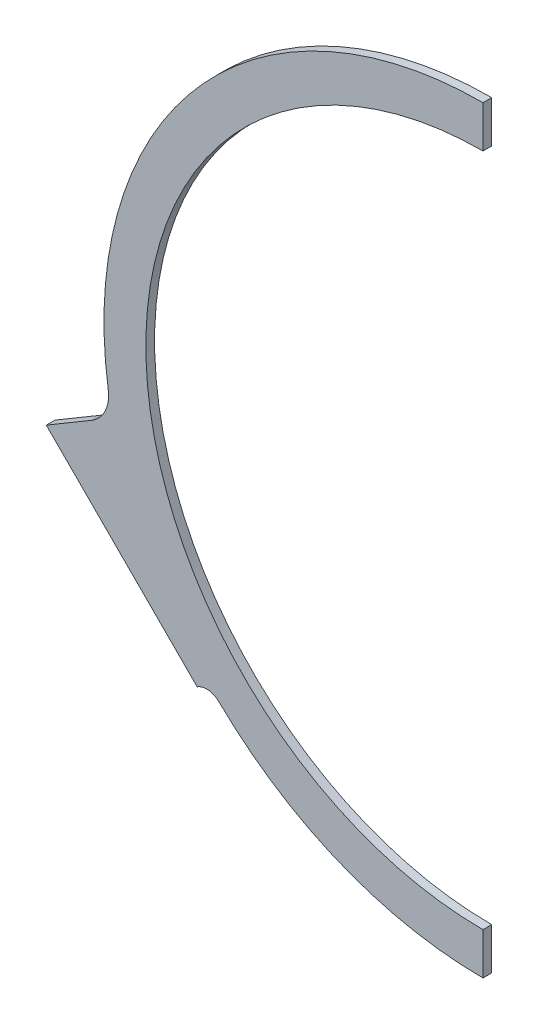
SolidWorks part; units mm, degrees
material "Balsa"
ref_plane "Front Plane" through (0, 0, 0) normal (0, 0, 1) x (1, 0, 0)
ref_plane "Top Plane" through (0, 0, 0) normal (0, 1, 0) x (1, 0, 0)
ref_plane "Right Plane" through (0, 0, 0) normal (1, 0, 0) x (0, 0, -1)
sketch "Sketch1" plane through (0, 0, 0) normal (0, 0, 1) x (1, 0, 0)
  line L0 (0, 0) -> (0, 499.9473) construction
  line L1 (0, -114.7984) -> (0, -129.4545) construction
  line L2 (0, -374.4718) -> (0, 404.2655) construction
  line L3 (-1.651, 142.9921) -> (-1.651, 150.6121) construction
  line L4 (1.651, 142.9921) -> (1.651, 150.6121) construction
  line L5 (-1.651, 142.9921) -> (1.651, 142.9921) construction
  line L6 (136.2041, -53.806) -> (0.0002, 24.7625) construction
  line L7 (-136.2076, -53.7991) -> (0.0002, 24.7625) construction
  line L8 (136.2041, -53.806) -> (0.0002, 24.7625) construction
  line L9 (-136.2076, -53.7991) -> (0.0002, 24.7625) construction
  line L10 (-125.0584, -45.4626) -> (-118.4576, -41.6554) construction
  line L11 (-123.6259, -48.4483) -> (-116.8078, -44.5157) construction
  line L12 (-118.4576, -41.6554) -> (-116.8078, -44.5157) construction
  line L13 (-124.1455, -48.7479) -> (-123.6847, -48.4822) construction
  line L14 (-123.6847, -48.4822) -> (-123.6259, -48.4483) construction
  line L15 (-125.7952, -45.8876) -> (-125.1113, -45.4931) construction
  line L16 (-125.1113, -45.4931) -> (-125.0584, -45.4626) construction
  line L17 (125.4797, -45.7137) -> (125.1075, -45.499) construction
  line L18 (123.8298, -48.5739) -> (123.6807, -48.488) construction
  line L19 (117.0223, -44.647) -> (118.6722, -41.7868) construction
  line L20 (123.6807, -48.488) -> (123.6228, -48.4545) construction
  line L21 (123.6228, -48.4545) -> (117.0223, -44.647) construction
  line L22 (125.1075, -45.499) -> (125.0554, -45.4689) construction
  line L23 (125.0554, -45.4689) -> (118.6722, -41.7868) construction
  line L24 (-107.079, -46.8884) -> (-120.3798, -54.5735)
  line L25 (-108.6638, -44.1348) -> (-121.9647, -51.8199)
  line L28 (-115.4206, -47.9666) -> (-121.9445, -51.7361) construction
  line L29 (-120.2754, -54.5131) -> (-108.646, -44.1245) construction
  line L30 (-114.4607, -49.3188) -> (-122.1124, -53.7399) construction
  line L31 (-113.7686, -50.8257) -> (-120.3665, -54.6379) construction
  line L32 (-115.4206, -47.9666) -> (-113.7686, -50.8257) construction
  line L33 (106.3137, -46.4532) -> (129.9098, -60.0883)
  line L34 (107.9004, -43.7007) -> (131.505, -57.3407)
  line L35 (129.9098, -60.0883) -> (131.505, -57.3407)
  line L36 (129.9098, -60.0883) -> (131.505, -57.3407) construction
  line L37 (107.9004, -43.7007) -> (131.505, -57.3407) construction
  line L38 (106.3137, -46.4532) -> (129.9098, -60.0883) construction
  line L39 (129.9098, -60.0883) -> (107.9004, -43.7007) construction
  line L40 (118.9051, -51.8945) -> (101.8722, -42.0519) construction
  line L41 (120.3631, -54.6438) -> (113.7655, -50.8313)
  line L42 (122.0152, -51.7848) -> (122.0057, -51.7794) construction
  line L43 (113.7655, -50.8313) -> (115.4176, -47.9723)
  line L44 (122.0057, -51.7794) -> (121.9413, -51.7421) construction
  line L45 (121.9413, -51.7421) -> (115.4176, -47.9723)
  line L46 (-108.6638, -44.1348) -> (-121.9647, -51.8199)
  line L47 (-107.079, -46.8884) -> (-120.3798, -54.5735)
  arc A0 (-1.651, 150.6121) -> (-125.0584, -45.4626) centre (0, 12.7) ccw
  circle A1 centre (0, 12.7) radius 120.904
  arc A2 (0, 150.622) -> (-1.651, 150.6121) centre (0, 12.7) ccw
  circle A3 centre (0, 12.7) radius 137.922 construction
  arc A4 (1.651, 150.6121) -> (0, 150.622) centre (0, 12.7) ccw
  arc A5 (-124.3508, -46.9604) -> (-123.6259, -48.4483) centre (0, 12.7) ccw
  arc A6 (-123.6259, -48.4483) -> (-121.9445, -51.7361) centre (0, 12.7) ccw
  arc A7 (-125.0584, -45.4626) -> (-124.3508, -46.9604) centre (0, 12.7) ccw
  arc A8 (124.3477, -46.9667) -> (125.0554, -45.4689) centre (0, 12.7) ccw
  arc A9 (125.0554, -45.4689) -> (1.651, 150.6121) centre (0, 12.7) ccw
  arc A10 (123.6228, -48.4545) -> (124.3477, -46.9667) centre (0, 12.7) ccw
  arc A11 (-121.9153, -51.7914) -> (-121.1641, -53.1919) centre (0, 12.7) ccw
  arc A12 (-120.3665, -54.6379) -> (120.3631, -54.6438) centre (0, 12.7) ccw
  arc A13 (-121.9445, -51.7361) -> (-121.9153, -51.7914) centre (0, 12.7) ccw
  arc A14 (-121.1641, -53.1919) -> (-120.3827, -54.6089) centre (0, 12.7) ccw
  arc A15 (-120.3827, -54.6089) -> (-120.397, -54.5834) centre (0, 12.7) ccw construction
  arc A16 (-120.397, -54.5834) -> (-120.3665, -54.6379) centre (0, 12.7) ccw construction
  arc A17 (120.3936, -54.5893) -> (121.0149, -53.4654) centre (0, 12.7) ccw construction
  arc A18 (121.9413, -51.7421) -> (123.6228, -48.4545) centre (0, 12.7) ccw
  arc A19 (120.3631, -54.6438) -> (120.3936, -54.5893) centre (0, 12.7) ccw construction
  arc A20 (121.0149, -53.4654) -> (121.9121, -51.7974) centre (0, 12.7) ccw construction
  arc A21 (121.9121, -51.7974) -> (121.9413, -51.7421) centre (0, 12.7) ccw construction
  spline S0 degree 3 poles (106.3137, -46.4532) (106.8426, -45.5357) (107.3715, -44.6182) (107.9004, -43.7007) knots 0 0 0 0 1 1 1 1 weights 1 1 1 1
  spline S1 degree 3 poles (-66.0123, 133.6164) (-70.0128, 131.4329) (-73.8716, 129.0699) (-81.3156, 123.9975) (-84.9009, 121.288) (-91.7995, 115.5249) (-95.113, 112.4712) (-99.0811, 108.4341) (-99.866, 107.6157) (-101.4182, 105.9565) (-102.1865, 105.1147) (-104.4569, 102.5643) (-105.9223, 100.8334) (-110.1768, 95.5512) (-115.4725, 88.2691) (-120.0285, 80.5179) (-123.1654, 74.5269) (-124.1643, 72.5002) (-125.5914, 69.415) (-126.0551, 68.3791) (-126.9587, 66.292) (-127.3989, 65.2397) (-129.5278, 59.9684) (-131.0098, 55.7) (-133.5456, 47.0638) (-134.5993, 42.696) (-136.2795, 33.8613) (-136.906, 29.3944) (-137.415, 23.7472) (-137.5031, 22.6146) (-137.6514, 20.3429) (-137.7116, 19.2049) (-137.8496, 15.7999) (-137.8852, 13.5361) (-137.8263, 6.7629) (-137.3062, -2.2197) (-135.9163, -11.1068) (-134.5433, -17.7359) (-134.0304, -19.9395) (-132.8922, -24.3345) (-132.2653, -26.5303) (-130.2347, -33.03) (-128.6774, -37.2656) (-126.1245, -43.2881) (-125.286, -45.1501) (-124.4066, -46.9926) knots 0 0 0 0 0.03125 0.03125 0.0625 0.0625 0.09375 0.09375 0.101563 0.101563 0.109375 0.109375 0.125 0.125 0.15625 0.1875 0.1875 0.203125 0.203125 0.210938 0.210938 0.21875 0.21875 0.25 0.25 0.28125 0.28125 0.3125 0.3125 0.320313 0.320313 0.328125 0.328125 0.34375 0.34375 0.375 0.40625 0.40625 0.421875 0.421875 0.4375 0.4375 0.46875 0.46875 0.48295 0.48295 0.48295 0.48295 construction
  spline S2 degree 3 poles (-1557.5256, 1030.3086) (-495.2142, -0.1753) (-82.1366, -210.7146) (81.4542, -98.9353) (85.033, -96.2237) (91.9188, -90.4573) (95.2258, -87.4025) (99.1858, -83.3647) (99.9691, -82.5461) (101.5182, -80.8868) (102.2849, -80.0449) (104.5506, -77.4941) (106.013, -75.7632) (110.2586, -70.4809) (112.9006, -66.8403) (117.8152, -59.3254) (120.0877, -55.4512) (123.2166, -49.4629) (124.2129, -47.4373) (125.6361, -44.3538) (126.0986, -43.3185) (126.9997, -41.2327) (127.4386, -40.181) (129.5618, -34.9121) (131.0396, -30.646) (133.5674, -22.0152) (134.6173, -17.6505) (136.2906, -8.8227) (136.914, -4.3596) (137.4197, 1.2823) (137.5071, 2.4139) (137.6542, 4.6834) (137.7138, 5.8206) (137.85, 9.2232) (137.8846, 11.4853) (137.8228, 18.2533) (137.2995, 27.2283) (135.9081, 36.1069) (134.5347, 42.7292) (134.0218, 44.9305) (132.8839, 49.3207) (132.2571, 51.5145) (130.2267, 58.0093) (128.67, 62.2416) (125.1615, 70.5162) (123.2097, 74.5586) (118.9108, 82.4534) (116.5637, 86.3058) (113.3753, 90.999) (112.7241, 91.9325) (111.3996, 93.7822) (110.7272, 94.697) (108.6802, 97.4113) (107.2757, 99.181) (102.9447, 104.3725) (96.8571, 110.9816) (90.1513, 116.9722) (84.8861, 121.2292) (83.0917, 122.6088) (80.3399, 124.6181) (79.4113, 125.2786) (77.543, 126.5731) (76.6028, 127.2075) (71.8708, 130.3161) (67.9881, 132.6004) (60.0328, 136.7739) (55.9603, 138.6631) (47.6249, 142.0446) (43.3619, 143.537) (37.9102, 145.1462) (36.8136, 145.4551) (34.6205, 146.0438) (33.5224, 146.3241) (30.2234, 147.1229) (28.0179, 147.5997) (21.3832, 148.8649) (16.9358, 149.4889) (7.993, 150.3014) (3.4975, 150.4899) (-3.2824, 150.4396) (-5.5486, 150.3672) (-10.0934, 150.1088) (-12.3559, 149.9236) (-19.101, 149.2046) (-23.5473, 148.5072) (-32.3412, 146.6856) (-36.6887, 145.5614) (-43.1354, 143.5526) (-45.2718, 142.8291) (-49.5193, 141.273) (-51.6323, 140.4395) (-274.1905, 46.1884) (-224.836, -608.7963) (101.1574, -1839.6029) knots -1.31339 -1.31339 -1.31339 -1.31339 0.03125 0.03125 0.0625 0.0625 0.09375 0.09375 0.101563 0.101563 0.109375 0.109375 0.125 0.125 0.15625 0.15625 0.1875 0.1875 0.203125 0.203125 0.210938 0.210938 0.21875 0.21875 0.25 0.25 0.28125 0.28125 0.3125 0.3125 0.320313 0.320313 0.328125 0.328125 0.34375 0.34375 0.375 0.40625 0.40625 0.421875 0.421875 0.4375 0.4375 0.46875 0.46875 0.5 0.5 0.53125 0.53125 0.539062 0.539062 0.546875 0.546875 0.5625 0.5625 0.59375 0.625 0.625 0.640625 0.640625 0.648437 0.648437 0.65625 0.65625 0.6875 0.6875 0.71875 0.71875 0.75 0.75 0.757812 0.757812 0.765625 0.765625 0.78125 0.78125 0.8125 0.8125 0.84375 0.84375 0.859375 0.859375 0.875 0.875 0.90625 0.90625 0.9375 0.9375 0.953125 0.953125 0.96875 0.96875 2.612134 2.612134 2.612134 2.612134 only from (66.1767, -108.566) to (-66.0123, 133.6164)
  spline S3 degree 3 poles (66.1767, -108.566) (70.1708, -106.3789) (74.0231, -104.0129) (81.4542, -98.9353) (85.033, -96.2237) (91.9188, -90.4573) (95.2258, -87.4025) (99.1858, -83.3647) (99.9691, -82.5461) (101.5182, -80.8868) (102.2849, -80.0449) (104.5506, -77.4941) (106.013, -75.7632) (110.2586, -70.4809) (112.9006, -66.8403) (117.8152, -59.3254) (120.0877, -55.4512) (123.2166, -49.4629) (124.2129, -47.4373) (125.6361, -44.3538) (126.0986, -43.3185) (126.9997, -41.2327) (127.4386, -40.181) (129.5618, -34.9121) (131.0396, -30.646) (133.5674, -22.0152) (134.6173, -17.6505) (136.2906, -8.8227) (136.914, -4.3596) (137.4197, 1.2823) (137.5071, 2.4139) (137.6542, 4.6834) (137.7138, 5.8206) (137.85, 9.2232) (137.8846, 11.4853) (137.8228, 18.2533) (137.2995, 27.2283) (135.9081, 36.1069) (134.5347, 42.7292) (134.0218, 44.9305) (132.8839, 49.3207) (132.2571, 51.5145) (130.2267, 58.0093) (128.67, 62.2416) (125.1615, 70.5162) (123.2097, 74.5586) (118.9108, 82.4534) (116.5637, 86.3058) (113.3753, 90.999) (112.7241, 91.9325) (111.3996, 93.7822) (110.7272, 94.697) (108.6802, 97.4113) (107.2757, 99.181) (102.9447, 104.3725) (96.8571, 110.9816) (90.1513, 116.9722) (84.8861, 121.2292) (83.0917, 122.6088) (80.3399, 124.6181) (79.4113, 125.2786) (77.543, 126.5731) (76.6028, 127.2075) (71.8708, 130.3161) (67.9881, 132.6004) (60.0328, 136.7739) (55.9603, 138.6631) (47.6249, 142.0446) (43.3619, 143.537) (37.9102, 145.1462) (36.8136, 145.4551) (34.6205, 146.0438) (33.5224, 146.3241) (30.2234, 147.1229) (28.0179, 147.5997) (21.3832, 148.8649) (16.9358, 149.4889) (7.993, 150.3014) (3.4975, 150.4899) (-3.2824, 150.4396) (-5.5486, 150.3672) (-10.0934, 150.1088) (-12.3559, 149.9236) (-19.101, 149.2046) (-23.5473, 148.5072) (-32.3412, 146.6856) (-36.6887, 145.5614) (-43.1354, 143.5526) (-45.2718, 142.8291) (-49.5193, 141.273) (-51.6323, 140.4395) (-57.9206, 137.7764) (-62.0153, 135.798) (-66.0123, 133.6164) knots 0 0 0 0 0.03125 0.03125 0.0625 0.0625 0.09375 0.09375 0.101563 0.101563 0.109375 0.109375 0.125 0.125 0.15625 0.15625 0.1875 0.1875 0.203125 0.203125 0.210938 0.210938 0.21875 0.21875 0.25 0.25 0.28125 0.28125 0.3125 0.3125 0.320313 0.320313 0.328125 0.328125 0.34375 0.34375 0.375 0.40625 0.40625 0.421875 0.421875 0.4375 0.4375 0.46875 0.46875 0.5 0.5 0.53125 0.53125 0.539062 0.539062 0.546875 0.546875 0.5625 0.5625 0.59375 0.625 0.625 0.640625 0.640625 0.648437 0.648437 0.65625 0.65625 0.6875 0.6875 0.71875 0.71875 0.75 0.75 0.757812 0.757812 0.765625 0.765625 0.78125 0.78125 0.8125 0.8125 0.84375 0.84375 0.859375 0.859375 0.875 0.875 0.90625 0.90625 0.9375 0.9375 0.953125 0.953125 0.96875 0.96875 1 1 1 1 construction
  spline S4 degree 3 poles (-124.4066, -46.9926) (-124.169, -47.4906) (-123.9283, -47.9871) (-123.6847, -48.4822) knots 0.48295 0.48295 0.48295 0.48295 0.486788 0.486788 0.486788 0.486788 construction
  spline S5 degree 3 poles (-123.6847, -48.4822) (-122.846, -50.1865) (-121.9718, -51.874) (-118.9108, -57.4955) (-116.5612, -61.3517) (-113.369, -66.0497) (-112.7169, -66.9844) (-111.3913, -68.8351) (-110.7184, -69.7503) (-108.6697, -72.4662) (-107.264, -74.2369) (-102.929, -79.4315) (-96.8353, -86.0447) (-90.1214, -92.0392) (-84.8493, -96.299) (-83.0524, -97.6795) (-80.2967, -99.6899) (-79.367, -100.3507) (-77.4971, -101.6451) (-76.5559, -102.2795) (-71.8198, -105.3881) (-67.9332, -107.6723) (-59.9695, -111.8452) (-55.8924, -113.7339) (-47.5468, -117.114) (-43.2782, -118.6053) (-37.8188, -120.2127) (-36.7216, -120.521) (-34.5268, -121.1085) (-33.4279, -121.3881) (-30.1264, -122.185) (-27.9191, -122.6605) (-21.2788, -123.9216) (-16.8274, -124.5426) (-7.8757, -125.3484) (-3.3755, -125.5332) (3.4122, -125.4766) (5.6812, -125.4019) (10.231, -125.1387) (12.493, -124.9512) (19.2413, -124.2249) (23.6899, -123.5224) (32.4889, -121.6898) (36.8393, -120.5597) (43.2904, -118.5412) (45.4283, -117.8143) (48.6163, -116.6419) (49.6759, -116.2374) (51.7885, -115.4006) (52.8426, -114.968) (58.0839, -112.7404) (62.1792, -110.755) (66.1767, -108.566) knots 0.486788 0.486788 0.486788 0.486788 0.5 0.5 0.53125 0.53125 0.539062 0.539062 0.546875 0.546875 0.5625 0.5625 0.59375 0.625 0.625 0.640625 0.640625 0.648437 0.648437 0.65625 0.65625 0.6875 0.6875 0.71875 0.71875 0.75 0.75 0.757812 0.757812 0.765625 0.765625 0.78125 0.78125 0.8125 0.8125 0.84375 0.84375 0.859375 0.859375 0.875 0.875 0.90625 0.90625 0.9375 0.9375 0.953125 0.953125 0.960937 0.960937 0.96875 0.96875 1 1 1 1 construction
  spline S6 degree 3 poles (-108.6638, -44.1348) (-108.1355, -45.0527) (-107.6073, -45.9705) (-107.079, -46.8884) knots 0 0 0 0 1 1 1 1 weights 1 1 1 1
  spline S7 degree 3 poles (-121.9647, -51.8199) (-121.4364, -52.7377) (-120.9081, -53.6556) (-120.3798, -54.5735) knots 0 0 0 0 1 1 1 1 weights 1 1 1 1
  spline S8 degree 3 poles (-893.3226, -1777.9828) (-225.0806, -622.1993) (441.4041, 533.982) (1105.2915, 1689.0999) knots -629.182553 -629.182553 -629.182553 -629.182553 630.825742 630.825742 630.825742 630.825742 weights 1.000316 0.999895 0.999895 1.000316 only from (106.3137, -46.4532) to (107.9004, -43.7007)
  spline S9 degree 3 poles (-121.8597, -51.7592) (-121.5948, -52.2177) (-121.3299, -52.6762) (-121.065, -53.1347) knots 0 0 0 0 0.5 0.5 0.5 0.5 weights 1 1 1 1 construction
  spline S12 degree 3 poles (-1117.6926, 1681.4946) (-455.9021, 527.2867) (209.8433, -629.4163) (878.1921, -1786.2645) knots -630.157908 -630.157908 -630.157908 -630.157908 629.848871 629.848871 629.848871 629.848871 weights 1.000509 0.999831 0.99983 1.000507 only from (-121.9647, -51.8199) to (-120.3798, -54.5735)
  spline S13 degree 3 poles (-1104.4721, 1689.253) (-442.507, 534.8951) (223.2028, -621.8101) (891.4356, -1778.7423) knots -630.135261 -630.135261 -630.135261 -630.135261 629.876801 629.876801 629.876801 629.876801 weights 1.000459 0.999847 0.999847 1.000457 only from (-108.6638, -44.1348) to (-107.079, -46.8884)
  point P7 (0, -125.5003)
  point P8 (0, 150.4602)
  point P25 (-125.0584, -45.4626)
  point P38 (123.6228, -48.4545)
  dimension "D2" = 275.844
  dimension "D1" = 275.9605
  dimension "D3" = 12.7
  dimension "D5" = 3.302
  dimension "D6" = 7.62
  dimension "D7" = 3.302
  dimension "D8" = 7.62
  dimension "D9" = 3.302
  dimension "D10" = 7.62
  dimension "D11" = 3.302
  dimension "D12" = 7.62
  dimension "D13" = 3.302
  dimension "D14" = 7.62
  dimension "D4" = 17.018
extrude "Boss-Extrude1" [suppressed] add sketch "Sketch1" along normal mid plane 3.175
sketch "Sketch2" plane through (248.2736, -245.0135, 0) normal (0, 0, -1) x (0, -1, 0)
  line L3 (-245.0135, 248.2736) -> (-427.6569, 248.2736) construction
  circle A1 centre (-257.7135, 248.2736) radius 137.922
  circle A16 centre (-257.7135, 248.2736) radius 122.682
  dimension "D1" = 12.7
  dimension "D2" = 275.844
  dimension "D3" = 15.24
fillet "Fillet1" [suppressed] radius 1.27
extrude "Boss-Extrude2" add sketch "Sketch2" along normal mid plane 3.175
sketch "Sketch3" plane through (0, 0, 0) normal (1, 0, 0) x (0, 0, -1)
  line L1 (-141.282, 263.3615) -> (149.6958, 263.3615)
  line L2 (-141.282, 263.3615) -> (-141.282, -241.4673)
  line L3 (-141.282, -241.4673) -> (149.6958, -241.4673)
  line L4 (149.6958, 263.3615) -> (149.6958, -241.4673)
extrude "Cut-Extrude1" cut sketch "Sketch3" along normal through all
sketch "Sketch4" plane through (0, 0, 0) normal (0, 0, 1) x (1, 0, 0)
  line L0 (0, 0) -> (-214.0513, 0) construction
  line L1 (-158.912, -30.4526) -> (-104.0071, -85.469)
  line L2 (-134.8591, -16.205) -> (-158.912, -30.4526)
  arc A0 (-104.0071, -85.469) -> (-167.1792, -137.0342) centre (409.8935, -779.5232) ccw construction
  arc A1 (0, 150.622) -> (0, -125.222) centre (0, 12.7) ccw construction
  arc A2 (-99.8692, -82.4242) -> (-104.0071, -85.469) centre (409.8935, -779.5232) ccw
  arc A3 (-134.8591, -16.205) -> (-99.8692, -82.4242) centre (0, 12.7) ccw
  point P6 (-99.8692, -82.4242)
  dimension "D3" = 54.61
  dimension "D5" = 863.6
  dimension "D1" = 99.8692
  dimension "D2" = 82.4242
  dimension "D4" = 67.31
  dimension "D6" = 45.058
  dimension "D7" = 133.9931
  dimension "D8" = 134.8591
  dimension "D9" = 30.64
extrude "Boss-Extrude3" add sketch "Sketch4" along normal mid plane 3.175
fillet "Fillet2" radius 6.35 1 edges at (-99.8692, -82.4242, 0)
fillet "Fillet3" radius 12.7 1 edges at (-134.8591, -16.205, 0)
equation "\"slotwidth\"=0.13"
equation "\"D11@Sketch1\"=\"slotwidth\""
